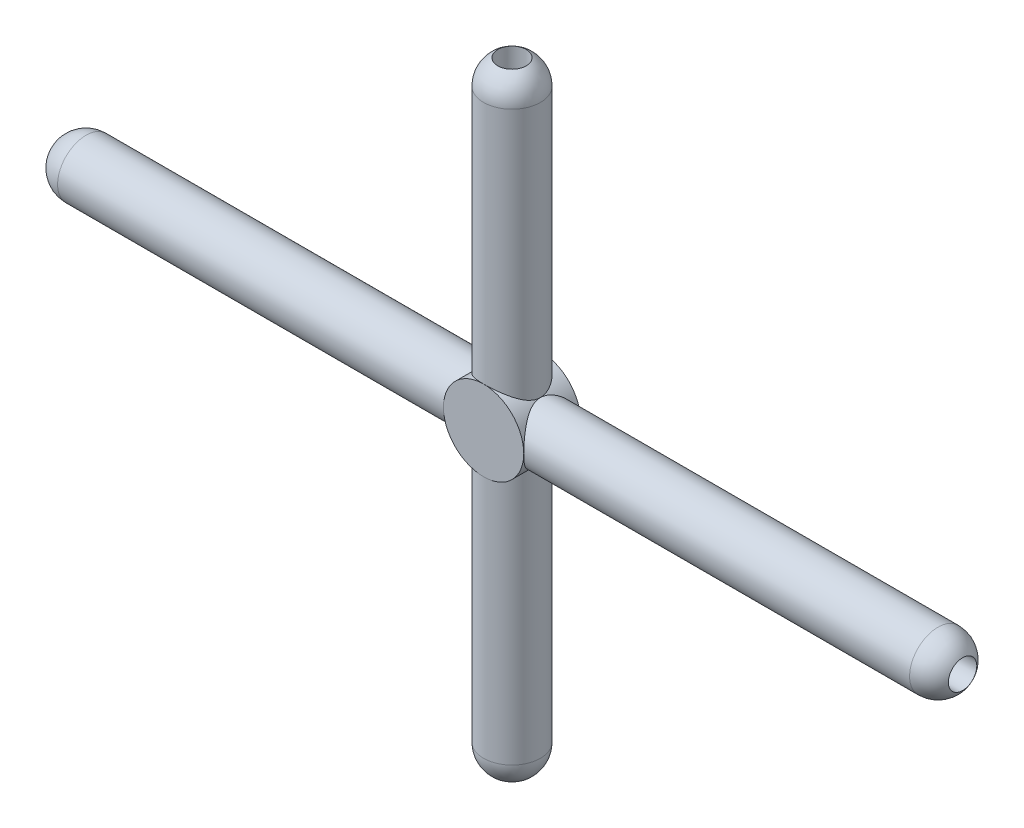
SolidWorks part; units mm, degrees
ref_plane "前视基准面" through (0, 0, 0) normal (0, 0, 1) x (1, 0, 0)
ref_plane "上视基准面" through (0, 0, 0) normal (0, 1, 0) x (1, 0, 0)
ref_plane "右视基准面" through (0, 0, 0) normal (1, 0, 0) x (0, 0, -1)
sketch "草图2" plane through (0, 0, 0) normal (0, 0, 1) x (1, 0, 0)
  line L0 (-265.8244, 0) -> (317.1005, 0) construction
  line L3 (-750, -50) -> (750, -50)
  line L7 (-750, 0) -> (750, 0)
  line L8 (-595.5365, 0) -> (-750, 0) construction
  line L9 (750, 0) -> (622.7751, 0) construction
  line L10 (-750, 0) -> (-800, 0)
  line L11 (750, 0) -> (800, 0)
  arc A0 (-800, 0) -> (-750, -50) centre (-750, 0) ccw
  arc A1 (750, -50) -> (800, 0) centre (750, 0) ccw
  point P0 (0, 0)
  dimension "D1" = 1500
  dimension "D2" = 750
  dimension "D3" = 50
revolve "旋转8" add sketch "草图2" angle 360 about L7
sketch "草图3" plane through (0, 0, 0) normal (0, 0, 1) x (1, 0, 0)
  line L0 (0, 0) -> (0, 500)
  line L2 (-50, 500) -> (-50, -500)
  line L4 (0, -500) -> (0, 0)
  line L5 (0, 500) -> (0, 626.3395) construction
  line L6 (0, -500) -> (0, -646.5942) construction
  line L7 (0, -500) -> (0, -550)
  line L8 (0, 500) -> (0, 550)
  arc A0 (0, 550) -> (-50, 500) centre (0, 500) ccw
  arc A1 (-50, -500) -> (0, -550) centre (0, -500) ccw
  dimension "D1" = 500
  dimension "D2" = 50
  dimension "D3" = 1000
revolve "旋转9" add sketch "草图3" angle 360 about L0
sketch "草图5" plane through (0, 0, 0) normal (0, 0, 1) x (1, 0, 0)
  circle A0 centre (0, 0) radius 70.7107
extrude "凸台-拉伸1" add sketch "草图5" along normal mid plane 100
sketch "草图6" plane through (0, 0, 0) normal (1, 0, 0) x (0, 0, -1)
  circle A0 centre (0, 0) radius 25
extrude "切除-拉伸1" cut sketch "草图6" along normal blind 842
pattern_circular "阵列(圆周)1" count 4 over 360 of "切除-拉伸1"
